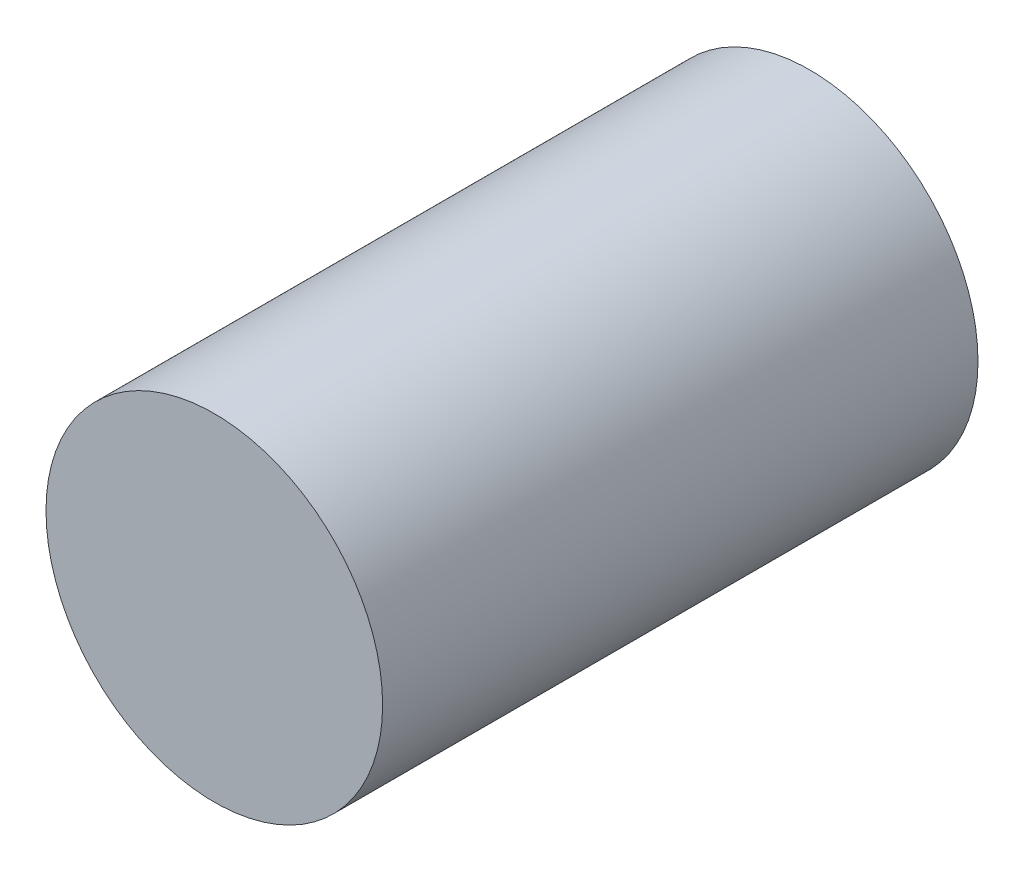
SolidWorks part; units mm, degrees
ref_plane "Front Plane" through (0, 0, 0) normal (0, 0, 1) x (1, 0, 0)
ref_plane "Top Plane" through (0, 0, 0) normal (0, 1, 0) x (1, 0, 0)
ref_plane "Right Plane" through (0, 0, 0) normal (1, 0, 0) x (0, 0, -1)
sketch "Sketch1" plane through (0, 0, 0) normal (0, 0, 1) x (1, 0, 0)
  circle A0 centre (0, 0) radius 33
  dimension "D1" = 66
extrude "Boss-Extrude1" add sketch "Sketch1" along normal blind 116.74
ref_axis "Axis1" through (0, 0, 174.5293) along (0, 0, -1)
